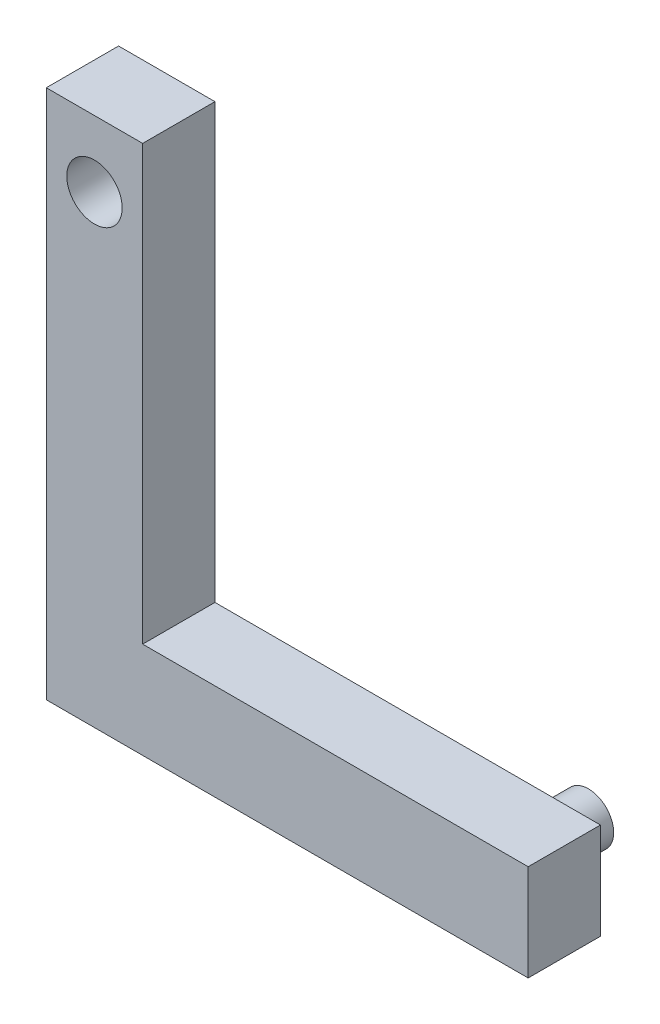
SolidWorks part; units mm, degrees
ref_plane "Alzado" through (0, 0, 0) normal (0, 0, 1) x (1, 0, 0)
ref_plane "Planta" through (0, 0, 0) normal (0, 1, 0) x (1, 0, 0)
ref_plane "Vista lateral" through (0, 0, 0) normal (1, 0, 0) x (0, 0, -1)
sketch "Croquis1" plane through (0, 0, 0) normal (0, 0, 1) x (1, 0, 0)
  line L1 (0, 0) -> (20, 0)
  line L2 (0, 0) -> (0, -4)
  line L3 (0, -4) -> (20, -4)
  line L4 (20, 0) -> (20, -4)
  circle A0 centre (0, -2.5) radius 1
  dimension "D5" = 2
  dimension "D1" = 4
  dimension "D2" = 20
  dimension "D3" = 20
  dimension "D4" = 2.5
extrude "Saliente-Extruir1" add sketch "Croquis1" along normal blind 3 contours L1 L4 L3 L2
sketch "Croquis3" plane through (0, 0, 0) normal (0, 0, -1) x (-1, 0, 0)
  line L0 (0, 0) -> (0, -4) construction
  line L1 (0, 0) -> (-20, 0) construction
  circle A0 centre (-17.5, -2) radius 1.05
  dimension "D3" = 2.1
  dimension "D1" = 17.5
  dimension "D2" = 2
sketch "Croquis4" plane through (0, 0, 0) normal (0, 0, -1) x (-1, 0, 0)
  line L0 (0, 0) -> (-20, 0) construction
  circle A0 centre (-2, -2) radius 1
  dimension "D2" = 2
  dimension "D3" = 2
sketch "Croquis5" plane through (0, 0, 3) normal (0, 0, 1) x (1, 0, 0)
  line L1 (0, 0) -> (4, 0)
  line L2 (0, 0) -> (0, 18)
  line L3 (0, 18) -> (4, 18)
  line L4 (4, 0) -> (4, 18)
  circle A0 centre (2, 15.25) radius 1.15
  circle A1 centre (2, -2) radius 1 construction
  line M9 (20, 0) -> (0, 0)
  dimension "D3" = 2.3
  dimension "D5" = 17.25
  dimension "D1" = 4
  dimension "D2" = 18
  dimension "D4" = 2
extrude "Saliente-Extruir2" add sketch "Croquis5" against normal blind 3 contours A0 | L4 L3 L2 A0 M9 region at (2, 8.6173, 3) region at (2, 15.25, 3)
extrude "Cortar-Extruir3" cut sketch "Croquis5<5>" against normal through all contours A0 region at (2, 15.25, 3)
sketch "Croquis5<5>" plane through (0, 0, 3) normal (0, 0, 1) x (1, 0, 0) same geometry as "Croquis5"
extrude "Saliente-Extruir4" add sketch "Croquis3" against normal blind 2
extrude "Saliente-Extruir5" add sketch "Croquis3<2>" along normal blind 2
sketch "Croquis3<2>" plane through (0, 0, 0) normal (0, 0, -1) x (-1, 0, 0) same geometry as "Croquis3"
